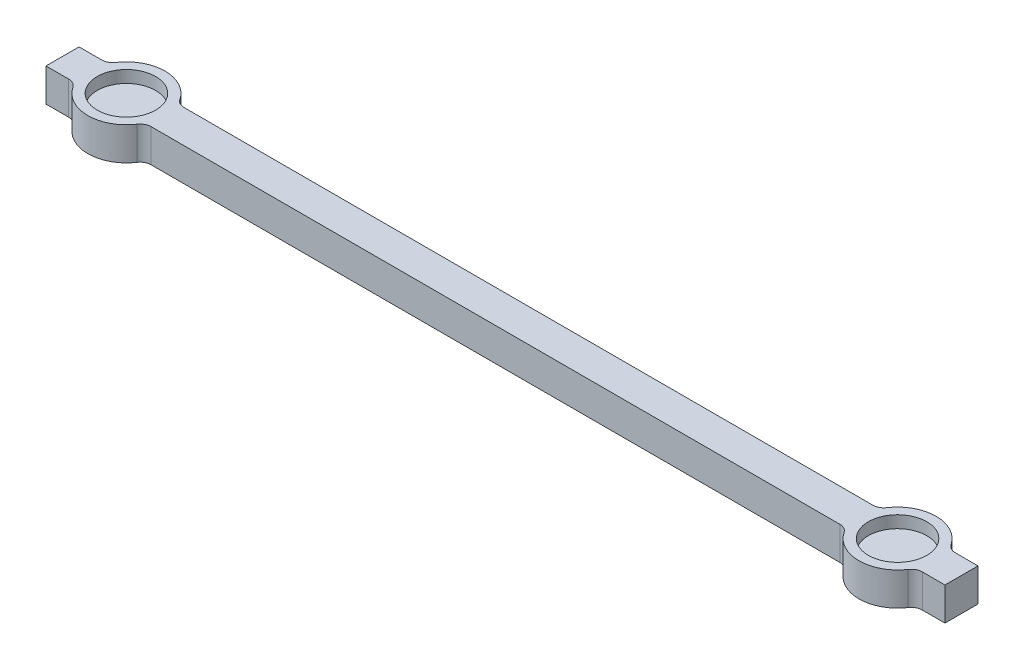
SolidWorks part; units mm, degrees
ref_plane "Front Plane" through (0, 0, 0) normal (0, 0, 1) x (1, 0, 0)
ref_plane "Top Plane" through (0, 0, 0) normal (0, 1, 0) x (1, 0, 0)
ref_plane "Right Plane" through (0, 0, 0) normal (1, 0, 0) x (0, 0, -1)
sketch "Sketch1" plane through (0, 0, 0) normal (0, 1, 0) x (1, 0, 0)
  line L0 (-40.8, 0) -> (40.8, 0) construction
  line L1 (-40.8, 3.5) -> (40.8, 3.5)
  line L2 (-40.8, 3.5) -> (-40.8, -3.5)
  line L3 (-40.8, -3.5) -> (40.8, -3.5)
  line L4 (40.8, 3.5) -> (40.8, -3.5)
  line L5 (-40.8, 3.5) -> (40.8, -3.5) construction
  line L6 (-40.8, -3.5) -> (40.8, 3.5) construction
  line L7 (0, 3.5) -> (0, -3.5) construction
  line L8 (-39.5, 3.5) -> (-39.5, -3.5) construction
  line L10 (40.8, 1.5) -> (-40.8, 1.5)
  line L11 (40.8, 1.5) -> (40.8, -1.5)
  line L12 (40.8, -1.5) -> (-40.8, -1.5)
  line L13 (-40.8, 1.5) -> (-40.8, -1.5)
  line L14 (40.8, 1.5) -> (-40.8, -1.5) construction
  line L15 (40.8, -1.5) -> (-40.8, 1.5) construction
  circle A0 centre (-35, 0) radius 2.5
  circle A1 centre (-35, 0) radius 3.5
  circle A2 centre (35, 0) radius 3.5
  point P0 (0, 0)
  point P15 (-37.5, 0)
  point P16 (0, 0)
  dimension "D3" = 5
  dimension "D1" = 81.6
  dimension "D2" = 7
  dimension "D4" = 1.3
  dimension "D5" = 2
  dimension "D6" = 3
extrude "Base shape" add sketch "Sketch1" along normal blind 3 contours A1 | L10 L13 L12 L11 | A2
sketch "Sketch2" plane through (0, 3, 0) normal (0, 1, 0) x (1, 0, 0)
  circle A0 centre (-35, 0) radius 2.65
  circle A1 centre (35, 0) radius 2.65
  dimension "D1" = 5.3
extrude "Magnet holes" cut sketch "Sketch2" against normal blind 1.1
fillet "Milling fillets" radius 1 8 edges at (31.8377, 1.5, -1.5) (-38.1623, 1.5, -1.5) (-31.8377, 1.5, -1.5) (38.1623, 1.5, -1.5) (38.1623, 1.5, 1.5) (31.8377, 1.5, 1.5) (-31.8377, 1.5, 1.5) (-38.1623, 1.5, 1.5)
sketch "Coordinate system sketch" plane through (0, 3, 0) normal (0, 1, 0) x (1, 0, 0)
  line L0 (35, -3.5) -> (40.8, -3.5) construction
  line L1 (40.8, -3.5) -> (40.8, -1.5) construction
  arc A0 (32.0898, -1.9444) -> (37.9102, -1.9444) centre (35, 0) ccw construction
  point P7 (0, 0)
